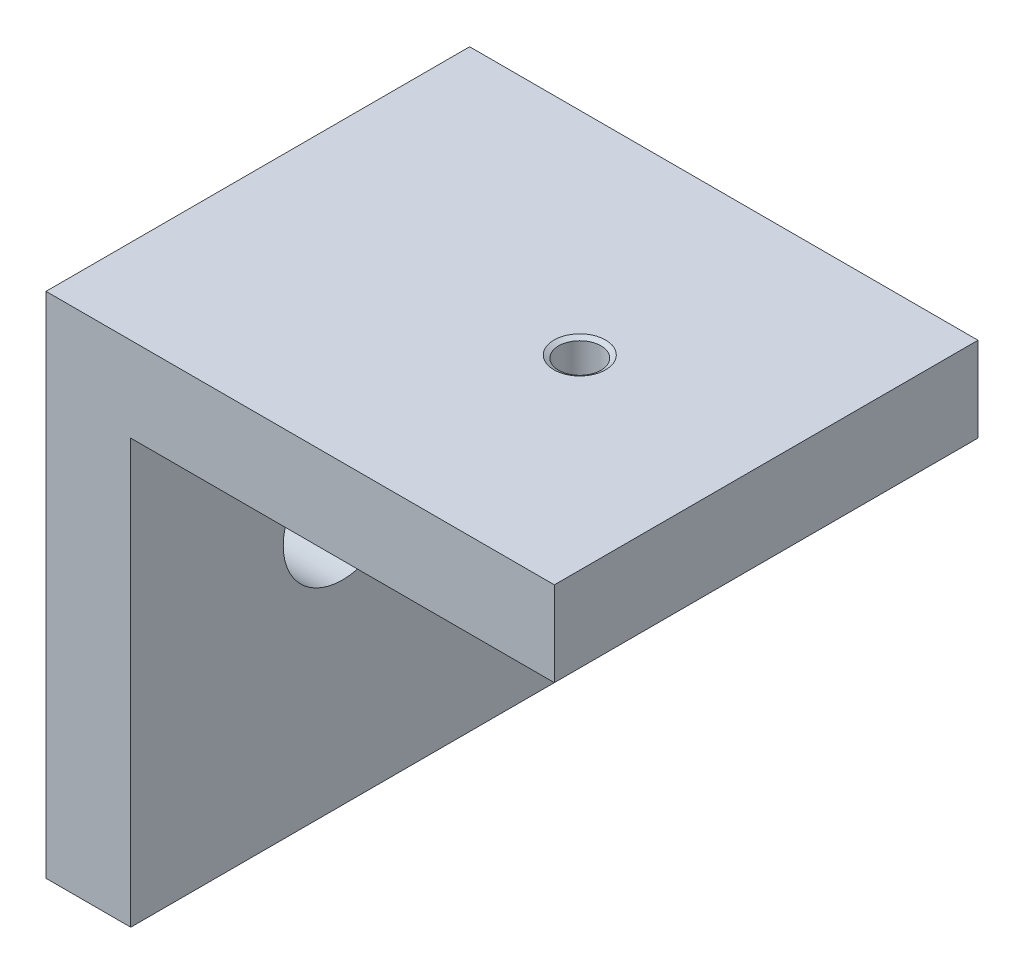
SolidWorks part; units mm, degrees
ref_plane "Piano frontale" through (0, 0, 0) normal (0, 0, 1) x (1, 0, 0)
ref_plane "Piano superiore" through (0, 0, 0) normal (0, 1, 0) x (1, 0, 0)
ref_plane "Piano destro" through (0, 0, 0) normal (1, 0, 0) x (0, 0, -1)
sketch "Schizzo1" plane through (0, 0, 0) normal (0, 0, 1) x (1, 0, 0)
  line L0 (0, 0) -> (0, 30)
  line L1 (0, 30) -> (30, 30)
  line L2 (30, 30) -> (30, 25)
  line L3 (30, 25) -> (5, 25)
  line L4 (5, 25) -> (5, 0)
  line L5 (5, 0) -> (0, 0)
  dimension "D1" = 30
  dimension "D2" = 5
  dimension "D3" = 30
  dimension "D4" = 5
extrude "Estrusione-Estrusione1" add sketch "Schizzo1" along normal blind 25
sketch "Schizzo2" plane through (0, 0, 0) normal (-1, 0, 0) x (0, 0, 1)
  line L0 (12.5, 0) -> (12.5, 16.7234) construction
  line L1 (25, 0) -> (0, 0) construction
  circle A0 centre (12.5, 15) radius 3.5
  dimension "D1" = 7
  dimension "D2" = 15
extrude "Taglio-Estrusione1" cut sketch "Schizzo2" against normal blind 25
sketch "Schizzo3" plane through (0, 30, 0) normal (0, 1, 0) x (1, 0, 0)
  line L0 (0, -12.5) -> (30, -12.5) construction
  line L1 (0, -25) -> (0, 0) construction
  line L2 (30, -25) -> (30, 0) construction
  point P6 (19, -12.5)
  dimension "D1" = 19
hole_wizard "Foro filettato M3-1" positions "Schizzo5" profile "Schizzo4" tap size "M3" standard "ISO"
sketch "Schizzo5" plane through (0, 30, 0) normal (0, 1, 0) x (1, 0, 0)
  point P0 (19, -12.5)
sketch "Schizzo4" plane through (19, 30, 12.5) normal (1, 0, 0) x (0, 0, 1)
  line L0 (0, 0) -> (0, 9.2511)
  line L1 (0, 9.2511) -> (1.25, 8.5)
  line L2 (1.25, 8.5) -> (1.25, 0.1588)
  line L3 (1.25, 0.1588) -> (1.525, 0)
  line L5 (1.525, 0) -> (0, 0)
  line L6 (-1.25, 0.1588) -> (-1.525, 0) construction
  line L10 (0, 9.2511) -> (-1.25, 8.5) construction
  line L11 (0, -6.35) -> (0, 107.95) construction
  dimension "Tap Drill Dia." = 2.5
  dimension "Tap Drill Depth" = 8.5
  dimension "Near C'Sink Dia." = 3.05
  dimension "Near C'Sink Angle" = 120
  dimension "Drill Angle" = 118
cosmetic thread "Filettatura del foro1" parameters "D1"=5, "D2"=3
